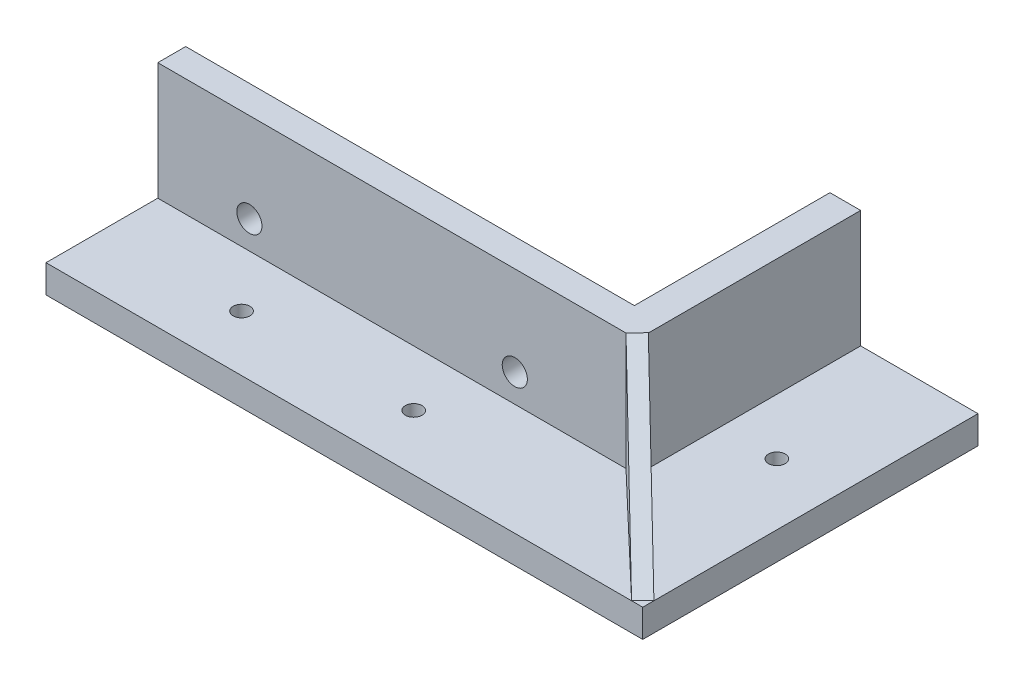
SolidWorks part; units mm, degrees
ref_plane "Front Plane" through (0, 0, 0) normal (0, 0, 1) x (1, 0, 0)
ref_plane "Top Plane" through (0, 0, 0) normal (0, 1, 0) x (1, 0, 0)
ref_plane "Right Plane" through (0, 0, 0) normal (1, 0, 0) x (0, 0, -1)
sketch "Croquis1" plane through (0, 0, 0) normal (0, 1, 0) x (1, 0, 0)
  line L0 (-40.4, -2.5) -> (-40.4, 2.5)
  line L1 (-40.4, -2.5) -> (40.4, -2.5)
  line L2 (-40.4, 2.5) -> (40.4, 2.5)
  line L3 (40.4, -2.5) -> (40.4, 2.5)
  line L4 (-40.4, -2.5) -> (40.4, 2.5) construction
  line L5 (-40.4, 2.5) -> (40.4, -2.5) construction
  line L6 (-40.4, -2.5) -> (-40.4, -22.5)
  line L7 (-40.4, -22.5) -> (40.4, -22.5)
  line L8 (40.4, -22.5) -> (40.4, -2.5)
  line L9 (-40.4, 2.5) -> (-40.4, 37.5)
  line L10 (-45.4, 37.5) -> (-45.4, -2.5)
  line L11 (-45.4, -2.5) -> (-40.4, -2.5)
  line L12 (-40.4, 37.5) -> (-66.4, 37.5)
  line L13 (-66.4, 37.5) -> (-66.4, -22.5)
  line L14 (-66.4, -22.5) -> (-40.4, -22.5)
  line L15 (0, 0) -> (0, 33.4342) construction
  line L16 (45.4, -2.5) -> (40.4, -2.5)
  line L17 (66.4, -22.5) -> (40.4, -22.5)
  line L18 (66.4, 37.5) -> (66.4, -22.5)
  line L19 (40.4, 37.5) -> (66.4, 37.5)
  line L20 (45.4, 37.5) -> (45.4, -2.5)
  line L21 (40.4, 37.5) -> (40.4, 2.5)
  circle A0 centre (-15.4, -12.5) radius 1.5
  circle A2 centre (-55.4, 12.5) radius 1.5
  circle A3 centre (15.4, -12.5) radius 1.5
  circle A4 centre (55.4, 12.5) radius 1.5
  point P1 (0, 0)
  dimension "D9" = 3
  dimension "D11" = 3
  dimension "D1" = 80.8
  dimension "D2" = 5
  dimension "D3" = 20
  dimension "D4" = 26
  dimension "D5" = 5
  dimension "D6" = 40
  dimension "D7" = 25
  dimension "D13" = 10
  dimension "D14" = 10
  dimension "D15" = 25
extrude "Saliente-Extruir1" add sketch "Croquis1" along normal blind 5 contours L7 L8 L1 L6 | L1 L3 L2 L0 region at (0, 0, 0) region at (0, 0, 12.5)
extrude "Saliente-Extruir2" add sketch "Croquis1<3>" along normal blind 26 contours L1 L3 L2 L0 region at (0, 0, 0)
sketch "Croquis1<3>" plane through (0, 0, 0) normal (0, 1, 0) x (1, 0, 0) same geometry as "Croquis1"
extrude "Saliente-Extruir3" add sketch "Croquis1<4>" along normal blind 5 contours L9 L12 L10 L11 L0 | L13 L14 L6 L11 L10 L12 A2 | L19 L20 L16 L8 L17 L18 A4 | L19 L21 L3 L16 L20 region at (-42.9, 0, -17.5) region at (-54.9417, 0, -5.9956) region at (54.9417, 0, -5.9956) region at (42.9, 0, -17.5)
sketch "Croquis1<4>" plane through (0, 0, 0) normal (0, 1, 0) x (1, 0, 0) same geometry as "Croquis1"
extrude "Saliente-Extruir4" add sketch "Croquis1<5>" along normal blind 26 contours L9 L12 L10 L11 L0 | L19 L21 L3 L16 L20 region at (-42.9, 0, -17.5) region at (42.9, 0, -17.5)
sketch "Croquis1<5>" plane through (0, 0, 0) normal (0, 1, 0) x (1, 0, 0) same geometry as "Croquis1"
sketch "Croquis3" plane through (0, 0, 2.5) normal (0, 0, 1) x (1, 0, 0)
  line L0 (45.4, 5) -> (-45.4, 5) construction
  line L1 (-45.4, 26) -> (-45.4, 5) construction
  line L2 (45.4, 26) -> (45.4, 5) construction
  circle A0 centre (-24, 10) radius 2.25
  circle A1 centre (23.5, 10) radius 2.25
  dimension "D5" = 4.5
  dimension "D6" = 4.5
  dimension "D1" = 5
  dimension "D2" = 5
  dimension "D3" = 21.4
  dimension "D4" = 21.9
extrude "Cortar-Extruir1" cut sketch "Croquis3" against normal blind 26
sketch "Croquis4" plane through (0, 5, 0) normal (0, 1, 0) x (1, 0, 0)
  line L0 (-45.4, -0.5) -> (-45.4, -2.5)
  line L1 (-45.4, -2.5) -> (-45.4, 37.5) construction
  line L2 (-45.4, -2.5) -> (-43.4, -2.5)
  line L3 (45.4, -2.5) -> (-45.4, -2.5) construction
  line L4 (-43.4, -2.5) -> (-64.4, -22.5)
  line L5 (-66.4, -22.5) -> (66.4, -22.5) construction
  line L6 (-64.4, -22.5) -> (-66.4, -22.5)
  line L7 (-66.4, -22.5) -> (-66.4, -20.5)
  line L8 (-66.4, 37.5) -> (-66.4, -22.5) construction
  line L9 (-66.4, -20.5) -> (-45.4, -0.5)
  dimension "D1" = 2
  dimension "D2" = 2
  dimension "D3" = 2
  dimension "D4" = 2
extrude "Saliente-Extruir5" add sketch "Croquis4" along normal blind 21
sketch "Croquis5" plane through (-19.3936, 0, -20.3633) normal (0.6897, 0, 0.7241) x (0.7241, 0, -0.6897)
  line L0 (-62.1517, 5) -> (-33.1517, 26)
  line L1 (-33.1517, 26) -> (-26.4869, 30.8262)
  line L2 (-26.4869, 30.8262) -> (-82.7596, 33.4038)
  line L3 (-82.7596, 33.4038) -> (-84.0606, 5)
  line L4 (-84.0606, 5) -> (-62.1517, 5)
extrude "Cortar-Extruir2" cut sketch "Croquis5" against normal blind 21
mirror "Simetría1" about plane through (0, 0, 0) normal (1, 0, 0) of "Saliente-Extruir5"
mirror "Simetría2" about plane through (0, 0, 0) normal (1, 0, 0) of "Cortar-Extruir2"
sketch "Croquis6" plane through (0, 0, -37.5) normal (0, 0, -1) x (-1, 0, 0)
  line L0 (40.4, 0) -> (40.4, 26)
  line L1 (40.4, 26) -> (78.3839, 26)
  line L2 (78.3839, 26) -> (78.3839, 0)
  line L3 (78.3839, 0) -> (40.4, 0)
extrude "Cortar-Extruir3" cut sketch "Croquis6" against normal blind 120
sketch "Croquis7" plane through (40.4, 0, 0) normal (-1, 0, 0) x (0, 0, 1)
  line L0 (-37.5, 26) -> (-2.5, 26)
  line L1 (-2.5, 26) -> (-2.5, 0)
  line L2 (-2.5, 0) -> (-37.5, 0)
  line L3 (-37.5, 0) -> (-37.5, 26)
extrude "Saliente-Extruir6" add sketch "Croquis7" along normal blind 0.5
